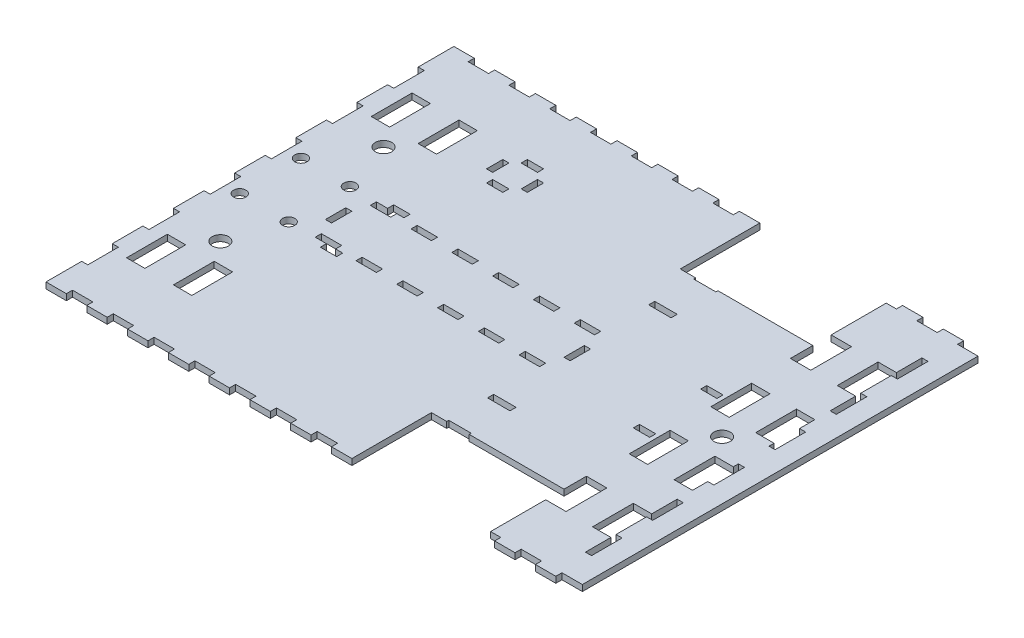
SolidWorks part; units mm, degrees
ref_plane "Front Plane" through (0, 0, 0) normal (0, 0, 1) x (1, 0, 0)
ref_plane "Top Plane" through (0, 0, 0) normal (0, 1, 0) x (1, 0, 0)
ref_plane "Right Plane" through (0, 0, 0) normal (1, 0, 0) x (0, 0, -1)
sketch "Sketch3" plane through (0, 0, 0) normal (0, 1, 0) x (1, 0, 0)
  line L0 (0, 0) -> (-300, 0) construction
  line L1 (-300, -97) -> (-300, 97)
  line L2 (-290, 100) -> (-300, 100)
  line L3 (-290, 97) -> (-290, 100)
  line L4 (-280, 97) -> (-290, 97)
  line L5 (-300, 100) -> (-300, 97)
  line L6 (-270, 100) -> (-280, 100)
  line L7 (-270, 97) -> (-270, 100)
  line L8 (-260, 97) -> (-270, 97)
  line L9 (-280, 100) -> (-280, 97)
  line L10 (-250, 100) -> (-260, 100)
  line L11 (-250, 97) -> (-250, 100)
  line L12 (-240, 97) -> (-250, 97)
  line L13 (-260, 100) -> (-260, 97)
  line L14 (-150, -100) -> (-150, 100) construction
  line L15 (-230, 100) -> (-240, 100)
  line L16 (-230, 97) -> (-230, 100)
  line L17 (-220, 97) -> (-230, 97)
  line L18 (-240, 100) -> (-240, 97)
  line L19 (-210, 100) -> (-220, 100)
  line L20 (-210, 97) -> (-210, 100)
  line L21 (-200, 97) -> (-210, 97)
  line L22 (-40, 97) -> (-40, -97)
  line L23 (-50, 37.5) -> (-53, 37.5)
  line L24 (-50, 7.5) -> (-53, 7.5)
  line L25 (-50, -45.947) -> (-50, 45.947) construction
  line L26 (-247, 37.5) -> (-250, 37.5) construction
  line L27 (-247, 7.5) -> (-250, 7.5) construction
  line L28 (-247, 48.5) -> (-247, -48.5) construction
  line L29 (-247, 48.5) -> (-223, 48.5) construction
  line L30 (-223, 48.5) -> (-223, -48.5) construction
  line L31 (-210, 15) -> (-90, 15) construction
  line L32 (-90, 15) -> (-90, 5) construction
  line L33 (-50, 7.5) -> (-50, 22.5)
  line L34 (-220, 100) -> (-220, 97)
  line L35 (-190, 100) -> (-200, 100)
  line L36 (-190, 97) -> (-190, 100)
  line L37 (-180, 97) -> (-190, 97)
  line L38 (-200, 100) -> (-200, 97)
  line L39 (-170, 100) -> (-180, 100)
  line L40 (-170, 97) -> (-170, 100)
  line L41 (-160, 97) -> (-170, 97)
  line L42 (-180, 100) -> (-180, 97)
  line L43 (-150, 100) -> (-160, 100)
  line L44 (-150, 97) -> (-150, 100)
  line L45 (-140, 97) -> (-150, 97)
  line L46 (-160, 100) -> (-160, 97)
  line L47 (-130, 100) -> (-140, 100)
  line L48 (-130, 97) -> (-130, 100)
  line L49 (-120, 97) -> (-130, 97)
  line L50 (-140, 100) -> (-140, 97)
  line L51 (-110, 100) -> (-120, 100)
  line L52 (-110, 97) -> (-110, 100)
  line L53 (-100, 97) -> (-110, 97)
  line L54 (-120, 100) -> (-120, 97)
  line L55 (-90, 100) -> (-100, 100)
  line L56 (-90, 97) -> (-90, 100)
  line L57 (-80, 97) -> (-90, 97)
  line L58 (-100, 100) -> (-100, 97)
  line L59 (-70, 100) -> (-80, 100)
  line L60 (-70, 97) -> (-70, 100)
  line L61 (-60, 97) -> (-70, 97)
  line L62 (-80, 100) -> (-80, 97)
  line L63 (-50, 100) -> (-60, 100)
  line L64 (-50, 97) -> (-50, 100)
  line L65 (-40, 97) -> (-50, 97)
  line L66 (-60, 100) -> (-60, 97)
  line L67 (-50, 22.5) -> (-53, 22.5)
  line L68 (-210, -15) -> (-90, -15) construction
  line L69 (-53, 7.5) -> (-53, 22.5)
  line L70 (-50, 37.5) -> (-50, 52.5)
  line L71 (-50, 52.5) -> (-53, 52.5)
  line L72 (-53, 37.5) -> (-53, 52.5)
  line L73 (-50, 67.5) -> (-53, 67.5)
  line L74 (-50, 67.5) -> (-50, 82.5)
  line L75 (-50, 82.5) -> (-53, 82.5)
  line L76 (-60, -100) -> (-60, -97)
  line L77 (-40, -97) -> (-50, -97)
  line L78 (-50, -97) -> (-50, -100)
  line L79 (-50, -100) -> (-60, -100)
  line L80 (-80, -100) -> (-80, -97)
  line L81 (-60, -97) -> (-70, -97)
  line L82 (-70, -97) -> (-70, -100)
  line L83 (-70, -100) -> (-80, -100)
  line L84 (-100, -100) -> (-100, -97)
  line L85 (-80, -97) -> (-90, -97)
  line L86 (-90, -97) -> (-90, -100)
  line L87 (-90, -100) -> (-100, -100)
  line L88 (-120, -100) -> (-120, -97)
  line L89 (-100, -97) -> (-110, -97)
  line L90 (-110, -97) -> (-110, -100)
  line L91 (-110, -100) -> (-120, -100)
  line L92 (-140, -100) -> (-140, -97)
  line L93 (-120, -97) -> (-130, -97)
  line L94 (-130, -97) -> (-130, -100)
  line L95 (-130, -100) -> (-140, -100)
  line L96 (-160, -100) -> (-160, -97)
  line L97 (-140, -97) -> (-150, -97)
  line L98 (-150, -97) -> (-150, -100)
  line L99 (-150, -100) -> (-160, -100)
  line L100 (-180, -100) -> (-180, -97)
  line L101 (-160, -97) -> (-170, -97)
  line L102 (-170, -97) -> (-170, -100)
  line L103 (-170, -100) -> (-180, -100)
  line L104 (-200, -100) -> (-200, -97)
  line L105 (-180, -97) -> (-190, -97)
  line L106 (-190, -97) -> (-190, -100)
  line L107 (-190, -100) -> (-200, -100)
  line L108 (-247, -48.5) -> (-223, -48.5) construction
  line L109 (-247, 7.5) -> (-247, 22.5) construction
  line L110 (-220, -100) -> (-220, -97)
  line L111 (-53, 67.5) -> (-53, 82.5)
  line L112 (-53, -67.5) -> (-53, -82.5)
  line L113 (-50, -82.5) -> (-53, -82.5)
  line L114 (-200, -97) -> (-210, -97)
  line L115 (-210, -97) -> (-210, -100)
  line L116 (-210, -100) -> (-220, -100)
  line L117 (-240, -100) -> (-240, -97)
  line L118 (-220, -97) -> (-230, -97)
  line L119 (-230, -97) -> (-230, -100)
  line L120 (-230, -100) -> (-240, -100)
  line L121 (-50, -67.5) -> (-50, -82.5)
  line L122 (-260, -100) -> (-260, -97)
  line L123 (-240, -97) -> (-250, -97)
  line L124 (-250, -97) -> (-250, -100)
  line L125 (-250, -100) -> (-260, -100)
  line L126 (-280, -100) -> (-280, -97)
  line L127 (-260, -97) -> (-270, -97)
  line L128 (-270, -97) -> (-270, -100)
  line L129 (-270, -100) -> (-280, -100)
  line L130 (-300, -100) -> (-300, -97)
  line L131 (-210, 15) -> (-210, -15) construction
  line L132 (-253, -15) -> (-243, -15)
  line L133 (-233, -15) -> (-223, -15)
  line L188 (-247, 22.5) -> (-250, 22.5) construction
  line L189 (-250, 7.5) -> (-250, 22.5) construction
  line L190 (-247, 37.5) -> (-247, 52.5) construction
  line L191 (-247, 52.5) -> (-250, 52.5) construction
  line L192 (-250, 37.5) -> (-250, 52.5) construction
  line L193 (-247, 67.5) -> (-250, 67.5) construction
  line L194 (-247, 67.5) -> (-247, 82.5) construction
  line L195 (-247, 82.5) -> (-250, 82.5) construction
  line L196 (-250, 67.5) -> (-250, 82.5) construction
  line L197 (-250, -67.5) -> (-250, -82.5) construction
  line L198 (-247, -82.5) -> (-250, -82.5) construction
  line L199 (-247, -67.5) -> (-247, -82.5) construction
  line L200 (-247, -67.5) -> (-250, -67.5) construction
  line L201 (-250, -37.5) -> (-250, -52.5) construction
  line L202 (-247, -52.5) -> (-250, -52.5) construction
  line L203 (-247, -37.5) -> (-247, -52.5) construction
  line L204 (-250, -7.5) -> (-250, -22.5) construction
  line L205 (-247, -22.5) -> (-250, -22.5) construction
  line L206 (-247, -7.5) -> (-247, -22.5) construction
  line L207 (-247, -7.5) -> (-250, -7.5) construction
  line L208 (-247, -37.5) -> (-250, -37.5) construction
  line L209 (-50, -67.5) -> (-53, -67.5)
  line L210 (-53, -37.5) -> (-53, -52.5)
  line L211 (-50, -52.5) -> (-53, -52.5)
  line L212 (-50, -37.5) -> (-50, -52.5)
  line L213 (-53, -7.5) -> (-53, -22.5)
  line L214 (-50, -22.5) -> (-53, -22.5)
  line L215 (-50, -7.5) -> (-50, -22.5)
  line L216 (-50, -7.5) -> (-53, -7.5)
  line L217 (-50, -37.5) -> (-53, -37.5)
  line L218 (-210, 0) -> (-258, 0)
  line L219 (-258, -5) -> (-255, -5)
  line L220 (-163, 15) -> (-173, 15)
  line L221 (-243, -12) -> (-243, -15)
  line L222 (-143, 15) -> (-143, 12)
  line L223 (-173, -15) -> (-173, -12)
  line L224 (-163, -15) -> (-173, -15)
  line L225 (-183, 12) -> (-183, 15)
  line L226 (-153, 15) -> (-153, 12)
  line L227 (-163, -12) -> (-163, -15)
  line L228 (-243, -12) -> (-253, -12)
  line L229 (-193, -15) -> (-193, -12)
  line L230 (-258, 5) -> (-255, 5)
  line L231 (-280, -97) -> (-290, -97)
  line L232 (-290, -97) -> (-290, -100)
  line L233 (-290, -100) -> (-300, -100)
  line L234 (-143, 15) -> (-153, 15)
  line L235 (-203, -12) -> (-213, -12)
  line L236 (-213, -15) -> (-213, -12)
  line L237 (-233, -15) -> (-233, -12)
  line L238 (-138, 5) -> (-141, 5)
  line L239 (-243, 12) -> (-243, 15)
  line L240 (-223, 12) -> (-223, 15)
  line L241 (-203, 12) -> (-213, 12)
  line L242 (-153, -15) -> (-153, -12)
  line L243 (-253, 15) -> (-253, 12)
  line L244 (-163, 12) -> (-163, 15)
  line L245 (-141, 5) -> (-141, -5)
  line L246 (-143, -15) -> (-143, -12)
  line L247 (-223, -12) -> (-233, -12)
  line L248 (-258, 15) -> (-258, -15) construction
  line L249 (-233, 15) -> (-233, 12)
  line L250 (-223, 15) -> (-233, 15)
  line L251 (-138, -5) -> (-141, -5)
  line L252 (-183, -15) -> (-193, -15)
  line L253 (-203, 15) -> (-213, 15)
  line L254 (-138, 5) -> (-138, -5)
  line L255 (-258, -15) -> (-138, -15) construction
  line L256 (-255, 5) -> (-255, -5)
  line L257 (-258, 5) -> (-258, -5)
  line L258 (-258, 15) -> (-138, 15) construction
  line L259 (-193, 15) -> (-193, 12)
  line L260 (-163, 12) -> (-173, 12)
  line L261 (-203, -15) -> (-213, -15)
  line L262 (-243, 12) -> (-253, 12)
  line L263 (-183, 15) -> (-193, 15)
  line L264 (-143, 12) -> (-153, 12)
  line L265 (-243, 15) -> (-253, 15)
  line L266 (-213, 15) -> (-213, 12)
  line L267 (-173, 15) -> (-173, 12)
  line L268 (-223, -12) -> (-223, -15)
  line L269 (-143, -12) -> (-153, -12)
  line L270 (-143, -15) -> (-153, -15)
  line L271 (-183, -12) -> (-193, -12)
  line L272 (-203, -12) -> (-203, -15)
  line L273 (-203, 12) -> (-203, 15)
  line L274 (-183, -12) -> (-183, -15)
  line L275 (-253, -15) -> (-253, -12)
  line L276 (-223, 12) -> (-233, 12)
  line L277 (-183, 12) -> (-193, 12)
  line L278 (-163, -12) -> (-173, -12)
  circle A0 centre (-290, 15) radius 3
  circle A1 centre (-266, 15) radius 3
  circle A2 centre (-266, -15) radius 3
  circle A3 centre (-290, -15) radius 3
  point P31 (-250, 36)
  point P80 (-91.5, 0)
  point P82 (-150, 0)
  point P126 (-223, 0)
  point P128 (-250, 18)
  point P129 (-50, 0)
  point P150 (-150, -15)
  point P151 (-150, 15)
  point P183 (-208.5, 0)
  point P212 (-223, 18)
  point P218 (-223, 36)
  point P235 (-198, -15)
  point P236 (-198, 15)
  dimension "D17" = 6
  dimension "D18" = 6
  dimension "D1" = 300
  dimension "D4" = 7.5
  dimension "D5" = 100
  dimension "D6" = 97
  dimension "D7" = 15
  dimension "D8" = 97
  dimension "D9" = 3
  dimension "D10" = 3
  dimension "D11" = 48.5
  dimension "D12" = 24
  dimension "D13" = 60
  dimension "D14" = 15
  dimension "D15" = 24
  dimension "D16" = 15
  dimension "D19" = 194
  dimension "D20" = 10
  dimension "D21" = 3
  dimension "D22" = 7.5
  dimension "D23" = 15
  dimension "D24" = 3
  dimension "D25" = 3
  dimension "D26" = 48
  dimension "D31" = 10
  dimension "D36" = 3
extrude "Boss-Extrude1" add sketch "Sketch3" along normal blind 3 contours L1 L116 L115 L107 L106 L83 L82 L79 L95 L98 L99 L91 L90 L86 region at (-170.2364, 0, 0)
sketch "Sketch5" plane through (0, 3, 0) normal (0, 1, 0) x (1, 0, 0)
  line L0 (-85, 0) -> (-85, 61) construction
  line L1 (-137, -60) -> (-137, -41)
  line L2 (-85, 61) -> (-131.5, 61)
  line L3 (-85, 61) -> (-85, 97)
  line L4 (-85, 97) -> (-150, 97)
  line L5 (-150, 61) -> (-150, 97)
  line L7 (-110, 100) -> (-120, 100) construction
  line L8 (-85, 0) -> (-300, 0) construction
  line L9 (-300, 100) -> (-300, -100) construction
  line L10 (-150, -61) -> (-150, -97)
  line L11 (-85, -97) -> (-150, -97)
  line L12 (-85, -61) -> (-85, -97)
  line L13 (-85, -61) -> (-131.5, -61)
  line L14 (-117.5, -61) -> (-117.5, -41) construction
  line L15 (-117.5, -41) -> (-131.5, -41) construction
  line L16 (-131.5, -41) -> (-131.5, -38)
  line L17 (-131.5, -38) -> (-142.5, -38)
  line L18 (-142.5, -38) -> (-142.5, -41)
  line L19 (-142.5, -41) -> (-131.5, -41)
  line L20 (-131.5, -61) -> (-131.5, -60)
  line L21 (-131.5, -60) -> (-142.5, -60)
  line L22 (-142.5, -60) -> (-142.5, -61)
  line L23 (-142.5, -61) -> (-150, -61)
  line L24 (-117.5, 41) -> (-131.5, 41) construction
  line L25 (-117.5, 61) -> (-117.5, 41) construction
  line L26 (-142.5, 60) -> (-142.5, 61)
  line L27 (-131.5, 60) -> (-142.5, 60)
  line L28 (-131.5, 61) -> (-131.5, 60)
  line L29 (-142.5, 41) -> (-131.5, 41)
  line L30 (-142.5, 38) -> (-142.5, 41)
  line L31 (-131.5, 38) -> (-142.5, 38)
  line L32 (-131.5, 41) -> (-131.5, 38)
  line L33 (-142.5, 61) -> (-150, 61)
  dimension "D1" = 19
  dimension "D2" = 36
  dimension "D3" = 3
  dimension "D5" = 14
  dimension "D6" = 3
  dimension "D7" = 11
  dimension "D9" = 1
extrude "Cut-Extrude2" cut sketch "Sketch5" against normal blind 10 contours L5 L2 L3 L4 | L12 L13 L10 L11 | L31 L30 L29 L32 | L17 L18 L19 L16 region at (-117.5912, 3, 78.9134) region at (-117.5912, 3, -78.9134) body kept at (-300, 0, -100)
sketch "Croquis1" plane through (0, 3, 0) normal (0, 1, 0) x (1, 0, 0)
  line L0 (-300, -67.5) -> (-300, -82.5)
  line L25 (-300, 100) -> (-300, -100) construction
  line L26 (-300, 37.5) -> (-300, 52.5)
  line L27 (-297, 37.5) -> (-300, 37.5)
  line L28 (-297, 7.5) -> (-300, 7.5)
  line L29 (-300, -7.5) -> (-297, -7.5)
  line L30 (-297, -22.5) -> (-300, -22.5)
  line L31 (-297, -7.5) -> (-297, -22.5)
  line L32 (-297, 82.5) -> (-297, 67.5)
  line L33 (-300, -22.5) -> (-300, -7.5)
  line L34 (-297, -37.5) -> (-297, -52.5)
  line L35 (-297, 67.5) -> (-300, 67.5)
  line L36 (-300, 67.5) -> (-300, 82.5)
  line L37 (-297, 52.5) -> (-297, 37.5)
  line L38 (-300, 22.5) -> (-297, 22.5)
  line L39 (-300, -37.5) -> (-297, -37.5)
  line L40 (-297, -52.5) -> (-300, -52.5)
  line L41 (-300, 52.5) -> (-297, 52.5)
  line L42 (-300, -52.5) -> (-300, -37.5)
  line L43 (-300, 82.5) -> (-297, 82.5)
  line L44 (-297, 22.5) -> (-297, 7.5)
  line L45 (-300, 7.5) -> (-300, 22.5)
  line L46 (-300, -67.5) -> (-297, -67.5)
  line L47 (-297, -67.5) -> (-297, -82.5)
  line L48 (-297, -82.5) -> (-300, -82.5)
  dimension "D1" = 15
  dimension "D2" = 15
extrude "Cortar-Extruir1" cut sketch "Croquis1" against normal blind 10
sketch "Croquis2" plane through (0, 3, 0) normal (0, 1, 0) x (1, 0, 0)
  line L0 (-40, 0) -> (-53, 0) construction
  line L1 (-40, 97) -> (-40, -97) construction
  line L2 (-53, 10) -> (-53, -10) construction
  line L3 (-53, -7.5) -> (-53, -22.5) construction
  line L4 (-53, -10) -> (-62, -10)
  line L5 (-62, -10) -> (-62, -30)
  line L6 (-62, -30) -> (-53, -30)
  line L7 (-53, -30) -> (-53, -10)
  line L8 (-53, -30) -> (-53, -50) construction
  line L9 (-53, -37.5) -> (-53, -52.5) construction
  line L10 (-53, -50) -> (-62, -50)
  line L11 (-62, -50) -> (-62, -70)
  line L12 (-62, -70) -> (-53, -70)
  line L13 (-53, -67.5) -> (-53, -82.5) construction
  line L14 (-53, -70) -> (-53, -50)
  line L15 (-53, 30) -> (-53, 50) construction
  line L16 (-53, 70) -> (-53, 50)
  line L17 (-62, 70) -> (-53, 70)
  line L18 (-62, 50) -> (-62, 70)
  line L19 (-53, 50) -> (-62, 50)
  line L20 (-53, 30) -> (-53, 10)
  line L21 (-62, 30) -> (-53, 30)
  line L22 (-62, 10) -> (-62, 30)
  line L23 (-53, 10) -> (-62, 10)
  line L24 (-62, 70) -> (-75, 70) construction
  line L25 (-75, 70) -> (-85, 70)
  line L26 (-75, 70) -> (-75, 50)
  line L27 (-75, 50) -> (-85, 50)
  line L28 (-85, 50) -> (-85, 70)
  line L29 (-75, 30) -> (-84, 30)
  line L30 (-84, 30) -> (-84, 10)
  line L31 (-84, 10) -> (-75, 10)
  line L32 (-75, 10) -> (-75, 30)
  line L33 (-75, -10) -> (-84, -10)
  line L34 (-84, -10) -> (-84, -30)
  line L35 (-84, -30) -> (-75, -30)
  line L36 (-75, -30) -> (-75, -10)
  line L37 (-75, -50) -> (-85, -50)
  line L38 (-85, -50) -> (-85, -70)
  line L39 (-85, -70) -> (-75, -70)
  line L40 (-75, -70) -> (-75, -50)
  line L41 (-266, 15) -> (-243.49, 15) construction
  line L42 (-68.5, 0) -> (-53, 0) construction
  line L43 (-243.49, 18) -> (-247.49, 18)
  line L44 (-247.49, 18) -> (-247.49, 15)
  line L45 (-290.5, 30) -> (-290.5, 50) construction
  line L46 (-290.5, -30) -> (-290.5, -50) construction
  line L47 (-247.49, 15) -> (-239.49, 15)
  line L48 (-239.49, 15) -> (-239.49, 18)
  line L49 (-267.5, -70) -> (-267.5, -50)
  line L50 (-258.5, -70) -> (-267.5, -70)
  line L51 (-258.5, -50) -> (-258.5, -70)
  line L52 (-267.5, -50) -> (-258.5, -50)
  line L53 (-239.49, 18) -> (-243.49, 18)
  line L54 (-68.5, 0) -> (-86, 0) construction
  line L55 (-239.49, -18) -> (-243.49, -18)
  line L56 (-239.49, -15) -> (-239.49, -18)
  line L57 (-247.49, -15) -> (-239.49, -15)
  line L58 (-247.49, -18) -> (-247.49, -15)
  line L59 (-243.49, -18) -> (-247.49, -18)
  line L60 (-86, 0) -> (-86, 15) construction
  line L61 (-258.5, 50) -> (-258.5, 70)
  line L62 (-267.5, 50) -> (-258.5, 50)
  line L63 (-267.5, 70) -> (-267.5, 50)
  line L64 (-267.5, 70) -> (-258.5, 70)
  line L65 (-86, 15) -> (-94, 15)
  line L66 (-94, 15) -> (-94, 18)
  line L67 (-94, 18) -> (-86, 18)
  line L68 (-86, 18) -> (-86, 15)
  line L69 (-290.5, 50) -> (-281.5, 50)
  line L70 (-281.5, 50) -> (-281.5, 70)
  line L71 (-281.5, 70) -> (-290.5, 70)
  line L72 (-290.5, 70) -> (-290.5, 50)
  line L73 (-290.5, -70) -> (-290.5, -50)
  line L74 (-281.5, -70) -> (-290.5, -70)
  line L75 (-281.5, -50) -> (-281.5, -70)
  line L76 (-290.5, -50) -> (-281.5, -50)
  line L77 (-86, -18) -> (-86, -15)
  line L78 (-86, -15) -> (-94, -15)
  line L79 (-94, -15) -> (-94, -18)
  line L80 (-94, -18) -> (-86, -18)
  line L81 (-230, 97) -> (-230, 60) construction
  line L82 (-240, 60) -> (-237, 60) construction
  line L83 (-234, 70) -> (-226, 70)
  line L84 (-240, 64) -> (-240, 56)
  line L85 (-220, 64) -> (-220, 56)
  line L86 (-234, 50) -> (-226, 50)
  line L89 (-237, 56) -> (-237, 64)
  line L90 (-237, 64) -> (-240, 64)
  line L91 (-237, 56) -> (-240, 56)
  line L92 (-230, 50) -> (-230, 53) construction
  line L93 (-230, 53) -> (-234, 53)
  line L94 (-234, 53) -> (-234, 50)
  line L95 (-230, 53) -> (-226, 53)
  line L96 (-226, 53) -> (-226, 50)
  line L97 (-230, 70) -> (-230, 67) construction
  line L98 (-226, 67) -> (-234, 67)
  line L99 (-234, 67) -> (-234, 70)
  line L100 (-223, 56) -> (-220, 56)
  line L101 (-223, 64) -> (-220, 64)
  line L102 (-223, 56) -> (-223, 64)
  line L103 (-226, 67) -> (-226, 70)
  circle A0 centre (-68.5, 0) radius 4
  circle A3 centre (-274.5, -40) radius 4
  circle A4 centre (-274.5, 40) radius 4
  dimension "D8" = 8
  dimension "D11" = 8
  dimension "D12" = 8
  dimension "D1" = 10
  dimension "D2" = 9
  dimension "D3" = 20
  dimension "D4" = 20
  dimension "D5" = 13
  dimension "D6" = 10
  dimension "D7" = 20
  dimension "D9" = 14
  dimension "D10" = 22.51
  dimension "D13" = 3
  dimension "D14" = 4
  dimension "D15" = 8
  dimension "D16" = 9
  dimension "D17" = 13
  dimension "D18" = 9
  dimension "D19" = 13
  dimension "D20" = 9
  dimension "D21" = 13
  dimension "D22" = 10
  dimension "D23" = 9
  dimension "D24" = 9
  dimension "D25" = 9
  dimension "D26" = 9
  dimension "D27" = 14
  dimension "D28" = 17.5
  dimension "D29" = 15.5
  dimension "D30" = 15
  dimension "D31" = 8
  dimension "D32" = 3
  dimension "D35" = 3
  dimension "D36" = 4
  dimension "D37" = 3
  dimension "D38" = 4
  dimension "D39" = 4
  dimension "D40" = 3
  dimension "D41" = 4
extrude "Cortar-Extruir2" cut sketch "Croquis2" against normal blind 10
